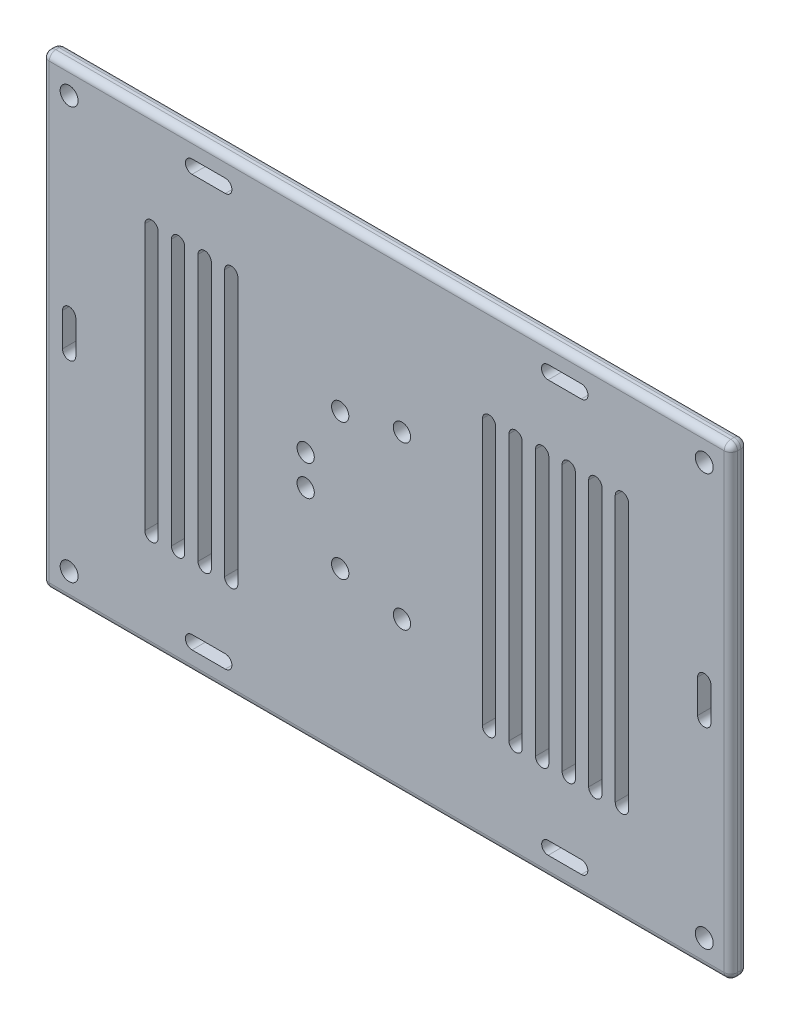
SolidWorks part; units mm, degrees
ref_plane "Plan de face" through (0, 0, 0) normal (0, 0, 1) x (1, 0, 0)
ref_plane "Plan de dessus" through (0, 0, 0) normal (0, 1, 0) x (1, 0, 0)
ref_plane "Plan de droite" through (0, 0, 0) normal (1, 0, 0) x (0, 0, -1)
sketch "Esquisse1" plane through (0, 0, 0) normal (0, 0, 1) x (1, 0, 0)
  line L0 (24.3, -31) -> (29.3, -31) construction
  line L1 (-51.8, 35) -> (51.8, 35)
  line L2 (-51.8, 35) -> (-51.8, -35)
  line L3 (-51.8, -35) -> (51.8, -35)
  line L4 (51.8, 35) -> (51.8, -35)
  line L5 (-51.8, 35) -> (51.8, -35) construction
  line L6 (-51.8, -35) -> (51.8, 35) construction
  line L7 (-47.8, 31) -> (47.8, 31) construction
  line L8 (-47.8, 31) -> (-47.8, -31) construction
  line L9 (-47.8, -31) -> (47.8, -31) construction
  line L10 (47.8, 31) -> (47.8, -31) construction
  line L11 (-47.8, 31) -> (47.8, -31) construction
  line L12 (-47.8, -31) -> (47.8, 31) construction
  line L15 (24.3, -30.0283) -> (29.3, -30.0283)
  line L16 (24.3, -31.9717) -> (29.3, -31.9717)
  line L17 (29.3, 31) -> (24.3, 31) construction
  line L20 (-29.3, -31) -> (-24.3, -31) construction
  line L21 (-29.3, -30) -> (-24.3, -30)
  line L22 (-29.3, -32) -> (-24.3, -32)
  line L23 (29.3, 30) -> (24.3, 30)
  line L24 (29.3, 32) -> (24.3, 32)
  line L25 (-29.3, 31) -> (-24.3, 31) construction
  line L26 (-29.3, 32) -> (-24.3, 32)
  line L27 (-29.3, 30) -> (-24.3, 30)
  line L28 (-47.8, 2.5) -> (-47.8, -2.5) construction
  line L29 (-46.8, 2.5) -> (-46.8, -2.5)
  line L30 (-48.8, 2.5) -> (-48.8, -2.5)
  line L31 (47.8, 2.5) -> (47.8, -2.5) construction
  line L32 (48.8, 2.5) -> (48.8, -2.5)
  line L33 (46.8, 2.5) -> (46.8, -2.5)
  arc A2 (24.3, -30.0283) -> (24.3, -31.9717) centre (24.3, -31) ccw
  arc A3 (29.3, -31.9717) -> (29.3, -30.0283) centre (29.3, -31) ccw
  arc A6 (-29.3, -30) -> (-29.3, -32) centre (-29.3, -31) ccw
  arc A7 (-24.3, -32) -> (-24.3, -30) centre (-24.3, -31) ccw
  arc A8 (29.3, 30) -> (29.3, 32) centre (29.3, 31) ccw
  arc A9 (24.3, 32) -> (24.3, 30) centre (24.3, 31) ccw
  arc A10 (-29.3, 32) -> (-29.3, 30) centre (-29.3, 31) ccw
  arc A11 (-24.3, 30) -> (-24.3, 32) centre (-24.3, 31) ccw
  arc A12 (-46.8, 2.5) -> (-48.8, 2.5) centre (-47.8, 2.5) ccw
  arc A13 (-48.8, -2.5) -> (-46.8, -2.5) centre (-47.8, -2.5) ccw
  arc A14 (48.8, 2.5) -> (46.8, 2.5) centre (47.8, 2.5) ccw
  arc A15 (46.8, -2.5) -> (48.8, -2.5) centre (47.8, -2.5) ccw
  point P0 (0, 0)
  point P5 (0, 0)
  point P6 (0, 0)
  point P13 (0, 0)
  point P14 (26.8, -31)
  point P22 (26.8, 31)
  point P28 (-26.8, -31)
  point P36 (-26.8, 31)
  point P43 (-47.8, 0)
  point P49 (47.8, 0)
  point P55 (0, 0)
  dimension "D5" = 25
  dimension "D6" = 5
  dimension "D7" = 5
  dimension "D8" = 25
  dimension "D9" = 25
  dimension "D11" = 25
  dimension "D1" = 70
  dimension "D2" = 103.6
  dimension "D3" = 4
  dimension "D4" = 4
  dimension "D10" = 5
  dimension "D12" = 5
extrude "Boss.-Extru.1" add sketch "Esquisse1" along normal blind 2.5
fillet "Congé3" radius 1 12 edges at (-51.8, 0, 2.5) (0, -35, 2.5) (0, 35, 2.5) (51.8, 0, 2.5) (51.8, -35, 1.25) (51.8, 35, 1.25) (-51.8, 35, 1.25) (-51.8, -35, 1.25) (51.8, 0, 0) (0, 35, 0) (-51.8, 0, 0) (0, -35, 0)
sketch "Esquisse36" plane through (0, 0, 2.5) normal (0, 0, 1) x (1, 0, 0)
  line L0 (25.4, 0) -> (0, 0) construction
  line L1 (50.8, -34) -> (50.8, 34) construction
  line L2 (50.8, 0) -> (25.4, 0) construction
  line L4 (35.4, -20) -> (15.4, -20) construction
  line L5 (35.4, -20) -> (35.4, 20) construction
  line L6 (35.4, 20) -> (15.4, 20) construction
  line L7 (15.4, -20) -> (15.4, 20) construction
  line L8 (35.4, -20) -> (15.4, 20) construction
  line L9 (35.4, 20) -> (15.4, -20) construction
  line L10 (35.4, 20) -> (35.4, -20) construction
  line L11 (36.4, 20) -> (36.4, -20)
  line L12 (34.4, 20) -> (34.4, -20)
  arc A0 (36.4, 20) -> (34.4, 20) centre (35.4, 20) ccw
  arc A1 (34.4, -20) -> (36.4, -20) centre (35.4, -20) ccw
  point P0 (25.4, 0)
  point P8 (35.4, 0)
  dimension "D1" = 20
  dimension "D2" = 40
extrude "Enlèv. mat.-Extru.2" cut sketch "Esquisse36" against normal through all
pattern_linear "Répétition linéaire1" count 6 spacing 4 along (-1, 0, 0) of "Enlèv. mat.-Extru.2"
sketch "Esquisse37" plane through (0, 0, 2.5) normal (0, 0, 1) x (1, 0, 0)
  line L0 (0, 0) -> (-50.8, 0) construction
  line L1 (-50.8, 34) -> (-50.8, -34) construction
  line L2 (-35.4, 20) -> (-35.4, -20) construction
  line L3 (-15.4, 20) -> (-35.4, 20) construction
  line L4 (-15.4, 20) -> (-15.4, -20) construction
  line L5 (-15.4, -20) -> (-35.4, -20) construction
  line L6 (-35.4, 20) -> (-35.4, -20) construction
  line L7 (-15.4, 20) -> (-35.4, -20) construction
  line L8 (-15.4, -20) -> (-35.4, 20) construction
  line L9 (-34.4, 20) -> (-34.4, -20)
  line L10 (-36.4, 20) -> (-36.4, -20)
  arc A0 (-34.4, 20) -> (-36.4, 20) centre (-35.4, 20) ccw
  arc A1 (-36.4, -20) -> (-34.4, -20) centre (-35.4, -20) ccw
  point P5 (-25.4, 0)
  point P11 (-35.4, 0)
  dimension "D1" = 40
  dimension "D2" = 20
extrude "Enlèv. mat.-Extru.3" cut sketch "Esquisse37" against normal through all
pattern_linear "Répétition linéaire2" count 4 spacing 4 along (1, 0, 0) of "Enlèv. mat.-Extru.3"
sketch "Esquisse48" plane through (0, 0, 2.5) normal (0, 0, 1) x (1, 0, 0)
  line L0 (51.8, 34) -> (51.8, -34) construction
  line L1 (-50.8, 35) -> (50.8, 35) construction
  line L2 (50.8, -35) -> (-50.8, -35) construction
  line L3 (-50.8, -35) -> (50.8, -35) construction
  line L6 (-51.8, -34) -> (-51.8, 34) construction
  circle A0 centre (-47.8, 31) radius 3
  circle A1 centre (-47.8, -31) radius 3
  circle A2 centre (47.8, 31) radius 3.3164
  circle A3 centre (47.8, -31) radius 3.4515
  dimension "D1" = 4
  dimension "D2" = 4
  dimension "D3" = 4
  dimension "D4" = 4
  dimension "D5" = 4
  dimension "D6" = 4
  dimension "D7" = 4
  dimension "D8" = 4
hole_wizard "Diamètre du perçage Ø2.7 (2.7)1" positions "Esquisse3D16" profile "Esquisse49" hole size "Ø2.7" standard "AS"
sketch3d "Esquisse3D16"
  point P0 (-47.8, 31, 2.5)
  point P3 (-47.8, -31, 2.5)
  point P6 (47.8, -31, 2.5)
  point P9 (47.8, 31, 2.5)
sketch "Esquisse49" plane through (-47.8, 31, 2.5) normal (1, 0, 0) x (0, -1, 0)
  line L0 (0, 0) -> (0, 5.8112)
  line L1 (0, 5.8112) -> (1.35, 5)
  line L2 (1.35, 5) -> (1.35, 0)
  line L5 (1.35, 0) -> (0, 0)
  line L10 (0, 5.8112) -> (-1.35, 5) construction
  line L11 (0, -6.35) -> (0, 107.95) construction
  dimension "Diamètre du perçage" = 2.7
  dimension "Profondeur du perçage" = 5
  dimension "Angle de pointe" = 118
sketch "Esquisse50" plane through (0, 0, 2.5) normal (0, 0, 1) x (1, 0, 0)
  line L1 (-7, 10.25) -> (7, 10.25) construction
  line L2 (-7, 10.25) -> (-7, -10.25) construction
  line L3 (-7, -10.25) -> (7, -10.25) construction
  line L4 (7, 10.25) -> (7, -10.25) construction
  line L5 (-7, 10.25) -> (7, -10.25) construction
  line L6 (-7, -10.25) -> (7, 10.25) construction
  line L7 (7, -10.25) -> (-7, -10.25)
  line L8 (7, -10.25) -> (7, 10.25)
  line L9 (7, 10.25) -> (-7, 10.25)
  line L10 (-7, -10.25) -> (-7, 10.25)
  line L11 (7, -10.25) -> (-7, 10.25) construction
  line L12 (7, 10.25) -> (-7, -10.25) construction
  circle A0 centre (-7, 10.25) radius 2.5
  circle A1 centre (-7, -10.25) radius 2.5
  point P0 (0, 0)
  point P6 (0, 0)
  dimension "D1" = 14
  dimension "D2" = 20.5
sketch "Esquisse52" plane through (0, 0, 2.5) normal (0, 0, 1) x (1, 0, 0)
  line L1 (-12.1976, 2.2981) -> (-2.2981, 12.1976) construction
  line L2 (-12.1976, 2.2981) -> (2.2981, -12.1976) construction
  line L3 (2.2981, -12.1976) -> (12.1976, -2.2981) construction
  line L4 (-2.2981, 12.1976) -> (12.1976, -2.2981) construction
  line L5 (-7, 10.25) -> (7, -10.25) construction
  line L6 (-7, -10.25) -> (7, 10.25) construction
  circle A0 centre (2.2981, -12.1976) radius 2.5
  circle A1 centre (-12.1976, 2.2981) radius 2.5
  point P0 (0, 0)
sketch "Esquisse54" plane through (0, 0, 2.5) normal (0, 0, 1) x (1, 0, 0)
  line L1 (-2.2981, -12.1976) -> (-12.1976, -2.2981) construction
  line L2 (-2.2981, -12.1976) -> (12.1976, 2.2981) construction
  line L3 (12.1976, 2.2981) -> (2.2981, 12.1976) construction
  line L4 (-12.1976, -2.2981) -> (2.2981, 12.1976) construction
  line L5 (7, -10.25) -> (-7, 10.25) construction
  line L6 (7, 10.25) -> (-7, -10.25) construction
  circle A0 centre (-12.1976, -2.2981) radius 2.5
  circle A1 centre (2.2981, 12.1976) radius 2.5
  point P0 (0, 0)
extrude "Boss.-Extru.2" add sketch "Esquisse52" against normal blind 7 contours A1 | A0
extrude "Boss.-Extru.3" add sketch "Esquisse50" against normal blind 7 contours A0 | A1
extrude "Boss.-Extru.4" add sketch "Esquisse54" against normal blind 7 contours A0 | A1
fillet "Congé4" radius 0.5 14 edges at (4.7981, 12.1976, 0) (4.7981, 12.1976, -4.5) (-4.5, 10.25, 0) (-4.5, 10.25, -4.5) (-12.1976, 4.7981, 0) (-12.1976, 4.7981, -4.5) (-13.1818, 0, -2.25) (-12.1976, -4.7981, 0) (-11.2133, 0, -2.25) (-12.1976, -4.7981, -4.5) (-4.5, -10.25, 0) (-4.5, -10.25, -4.5) (4.7981, -12.1976, 0) (4.7981, -12.1976, -4.5)
hole_wizard "Diamètre du perçage Ø2.6 (2.6)3" positions "Esquisse3D20" profile "Esquisse60" hole size "Ø2.6" standard "AS"
sketch3d "Esquisse3D20"
  line L0 (2.2981, -12.1976, -5.4177) -> (2.2981, -12.1976, -1.1645) construction
  line L1 (-7, -10.25, -5.4177) -> (-7, -10.25, -1.1645) construction
  line L2 (2.2981, 12.1976, -5.4177) -> (2.2981, 12.1976, -1.1645) construction
  line L3 (-7, 10.25, -5.4177) -> (-7, 10.25, -1.1645) construction
  line L4 (-12.1976, 2.2981, -5.3378) -> (-12.1976, 2.2981, -1.3244) construction
  line L5 (-12.1976, -2.2981, -5.3378) -> (-12.1976, -2.2981, -1.3244) construction
  point P0 (2.2981, -12.1976, -4.5)
  point P4 (-7, -10.25, -4.5)
  point P8 (2.2981, 12.1976, -4.5)
  point P12 (-7, 10.25, -4.5)
  point P16 (-12.1976, 2.2981, -4.5)
  point P20 (-12.1976, -2.2981, -4.5)
sketch "Esquisse60" plane through (2.2981, -12.1976, -4.5) normal (1, 0, 0) x (0, 1, 0)
  line L0 (0, 0) -> (0, 15.7811)
  line L1 (0, 15.7811) -> (1.3, 15)
  line L2 (1.3, 15) -> (1.3, 0)
  line L5 (1.3, 0) -> (0, 0)
  line L10 (0, 15.7811) -> (-1.3, 15) construction
  line L11 (0, -6.35) -> (0, 107.95) construction
  dimension "Diamètre du perçage" = 2.6
  dimension "Profondeur du perçage" = 15
  dimension "Angle de pointe" = 118
fillet "Congé5" radius 0.5 6 edges at (0.9981, -12.1976, -4.5) (-13.4976, -2.2981, -4.5) (-13.4976, 2.2981, -4.5) (-8.3, 10.25, -4.5) (0.9981, 12.1976, -4.5) (-8.3, -10.25, -4.5)
